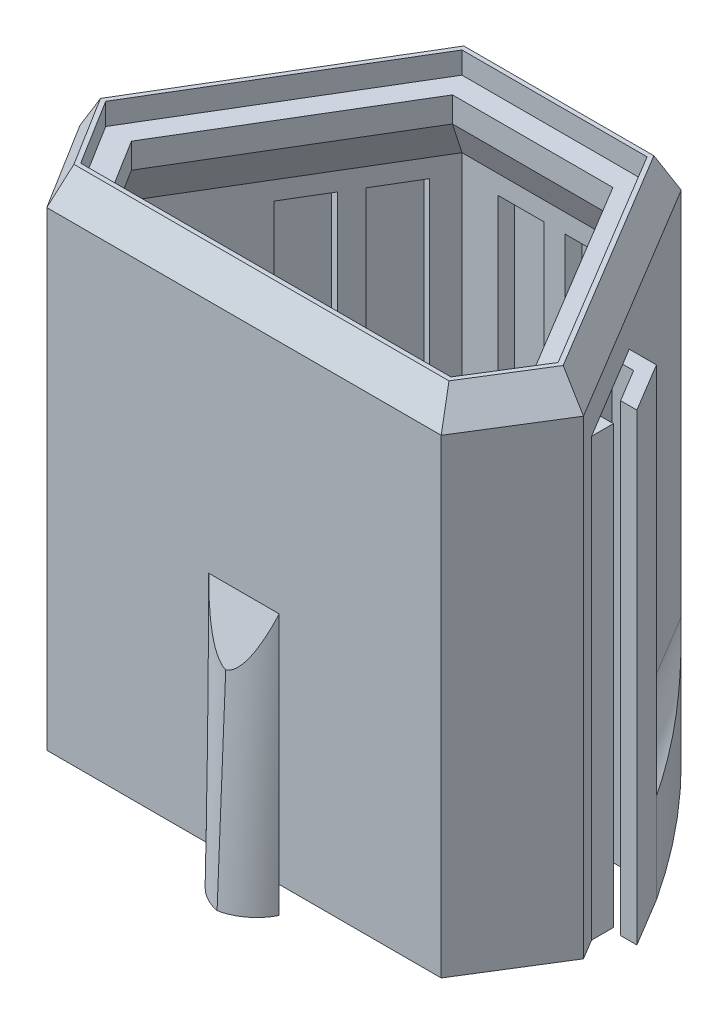
SolidWorks part; units mm, degrees
ref_plane "Front Plane" through (0, 0, 0) normal (0, 0, 1) x (1, 0, 0)
ref_plane "Top Plane" through (0, 0, 0) normal (0, 1, 0) x (1, 0, 0)
ref_plane "Right Plane" through (0, 0, 0) normal (1, 0, 0) x (0, 0, -1)
sketch "Sketch1" plane through (0, 0, 0) normal (0, 1, 0) x (1, 0, 0)
  line L0 (-12.5, 39.6) -> (12.5, 39.6)
  line L1 (-23.5, 0) -> (23.5, 0)
  line L2 (-11.0283, 37) -> (11.0283, 37)
  line L3 (11.0283, 37) -> (26.953, 10.474)
  line L4 (22.0553, 2.6) -> (26.953, 10.474)
  line L5 (-23.5, 0) -> (-30, 10.45)
  line L6 (-12.5, 39.6) -> (-30, 10.45)
  line L7 (12.5, 39.6) -> (30, 10.45)
  line L8 (23.5, 0) -> (30, 10.45)
  line L9 (-22.0553, 2.6) -> (22.0553, 2.6)
  line L10 (-22.0553, 2.6) -> (-26.953, 10.474)
  line L11 (-11.0283, 37) -> (-26.953, 10.474)
  dimension "D1" = 2.6
extrude "Boss-Extrude1" add sketch "Sketch1" along normal blind 60
sketch "Sketch4" plane through (0, 60, 0) normal (0, 1, 0) x (1, 0, 0)
  line L27 (-23.906, 10.4981) -> (-20.6106, 5.2)
  line L28 (-20.6106, 5.2) -> (20.6106, 5.2)
  line L29 (20.6106, 5.2) -> (23.906, 10.4981)
  line L30 (23.906, 10.4981) -> (9.5567, 34.4)
  line L31 (9.5567, 34.4) -> (-9.5567, 34.4)
  line L32 (-9.5567, 34.4) -> (-23.906, 10.4981)
  line L33 (-23.906, 10.4981) -> (-20.6106, 5.2)
  line L34 (-20.6106, 5.2) -> (20.6106, 5.2)
  line L35 (20.6106, 5.2) -> (23.906, 10.4981)
  line L36 (23.906, 10.4981) -> (9.5567, 34.4)
  line L37 (9.5567, 34.4) -> (-9.5567, 34.4)
  line L38 (-9.5567, 34.4) -> (-23.906, 10.4981)
  line L39 (-26.953, 10.474) -> (-22.0553, 2.6)
  line L43 (11.0283, 37) -> (-11.0283, 37)
  line L44 (-22.0553, 2.6) -> (22.0553, 2.6)
  line L45 (22.0553, 2.6) -> (26.953, 10.474)
  line L46 (26.953, 10.474) -> (11.0283, 37)
  line L47 (-11.0283, 37) -> (-26.953, 10.474)
  line L48 (11.0283, 37) -> (-11.0283, 37)
  line L49 (-22.0553, 2.6) -> (22.0553, 2.6)
  line L50 (22.0553, 2.6) -> (26.953, 10.474)
  line L51 (26.953, 10.474) -> (11.0283, 37)
  line L52 (-11.0283, 37) -> (-26.953, 10.474)
  line M18 (-22.0553, 2.6) -> (-26.953, 10.474)
  line M19 (-26.953, 10.474) -> (-11.0283, 37)
  line M20 (-11.0283, 37) -> (11.0283, 37)
  line M21 (11.0283, 37) -> (26.953, 10.474)
  line M22 (26.953, 10.474) -> (22.0553, 2.6)
  line M23 (22.0553, 2.6) -> (-22.0553, 2.6)
  dimension "D1" = 2.6
  dimension "D2" = 0
extrude "Boss-Extrude2" add sketch "Sketch4" against normal blind 10.6 contours L38 L37 L36 L35 L34 L33 M18 M23 M22 M21 M20 M19 region at (-18.4424, 60, -23.4079)
chamfer "Chamfer2" distance 4 distance2 2.08 6 edges at (26.75, 60, -5.225) (0, 60, 0) (-26.75, 60, -5.225) (-21.25, 60, -25.025) (0, 60, -39.6) (21.25, 60, -25.025) first distance on face at (26.75, 30, -5.225) first distance on face at (0, 30, 0) first distance on face at (-26.75, 30, -5.225) first distance on face at (-21.25, 30, -25.025) first distance on face at (0, 30, -39.6) first distance on face at (21.25, 30, -25.025)
sketch "Sketch5" plane through (0, 60, 0) normal (0, 1, 0) x (1, 0, 0)
  line L34 (-11.0283, 37) -> (-26.953, 10.474)
  line L35 (-26.953, 10.474) -> (-22.0553, 2.6)
  line L36 (-22.0553, 2.6) -> (22.0553, 2.6)
  line L37 (22.0553, 2.6) -> (26.953, 10.474)
  line L38 (26.953, 10.474) -> (11.0283, 37)
  line L39 (11.0283, 37) -> (-11.0283, 37)
  line L40 (-23.906, 10.4981) -> (-20.6106, 5.2)
  line L41 (-20.6106, 5.2) -> (20.6106, 5.2)
  line L42 (20.6106, 5.2) -> (23.906, 10.4981)
  line L43 (23.906, 10.4981) -> (9.5567, 34.4)
  line L44 (9.5567, 34.4) -> (-9.5567, 34.4)
  line L45 (-9.5567, 34.4) -> (-23.906, 10.4981)
  line L46 (-23.906, 10.4981) -> (-20.6106, 5.2)
  line L47 (-20.6106, 5.2) -> (20.6106, 5.2)
  line L48 (20.6106, 5.2) -> (23.906, 10.4981)
  line L49 (23.906, 10.4981) -> (9.5567, 34.4)
  line L50 (9.5567, 34.4) -> (-9.5567, 34.4)
  line L51 (-9.5567, 34.4) -> (-23.906, 10.4981)
  dimension "D1" = 0
  dimension "D2" = 2.6
extrude "Cut-Extrude1" cut sketch "Sketch5" against normal blind 2.6
sketch "Sketch6" plane through (0, 0, 0) normal (0, -1, 0) x (-1, 0, 0)
  line L0 (-28.5531, 12.8601) -> (-26.9922, 15.4601)
  line L1 (-28.5531, 12.8601) -> (-28.5531, 15.4601)
  line L2 (-28.5531, 15.4601) -> (-26.9922, 15.4601)
extrude "Boss-Extrude3" add sketch "Sketch6" against normal blind 52
sketch "Sketch7" plane through (0, 0, 0) normal (0, -1, 0) x (-1, 0, 0)
  line L0 (-26.9922, 15.4601) -> (-25.6922, 15.4601)
  line L1 (-26.9922, 15.4601) -> (-22.9775, 22.1475)
  line L2 (-26.9922, 15.4601) -> (-12.5, 39.6) construction
  line L3 (-22.9775, 22.1475) -> (-21.6775, 22.1475)
  line L4 (-21.6775, 22.1475) -> (-25.6922, 15.4601)
  dimension "D1" = 1.3
  dimension "D2" = 4.0148
extrude "Cut-Extrude2" cut sketch "Sketch7" against normal blind 52
sketch "Sketch8" plane through (0, 0, 0) normal (0, -1, 0) x (1, 0, 0)
  line L0 (22.9775, -22.1475) -> (24.2775, -22.1475)
  line L1 (24.2775, -22.1475) -> (26.6113, -18.2601)
  line L2 (21.8117, -24.0894) -> (22.9775, -22.1475)
  line L3 (26.6113, -18.2601) -> (28.5531, -18.2601)
  line L4 (28.5531, -18.2601) -> (25.0535, -24.0894)
  line L5 (25.0535, -24.0894) -> (21.8117, -24.0894)
  line L6 (22.9775, -22.1475) -> (12.5, -39.6) construction
extrude "Boss-Extrude4" add sketch "Sketch8" against normal blind 52
mirror "Mirror1" about plane through (0, 0, 0) normal (1, 0, 0) of "Boss-Extrude3", "Cut-Extrude2", "Boss-Extrude4"
chamfer "Chamfer3" distance 5 distance2 2.6 6 edges at (0, 49.4, -5.2) (22.2583, 49.4, -7.849) (16.7314, 49.4, -22.449) (0, 49.4, -34.4) (-22.2583, 49.4, -7.849) (-16.7314, 49.4, -22.449) first distance on face at (0, 53.4, -5.2) first distance on face at (22.2583, 53.4, -7.849) first distance on face at (16.7314, 53.4, -22.449) first distance on face at (0, 53.4, -34.4) first distance on face at (-22.2583, 53.4, -7.849) first distance on face at (-16.7314, 53.4, -22.449)
sketch "Sketch10" plane through (0, 0, 0) normal (0, -1, 0) x (1, 0, 0)
  line L0 (-12.5, -39.6) -> (-19.6941, -27.6167)
  line L1 (-25.0535, -24.0894) -> (-28.5531, -18.2601)
  line L2 (-28.5531, -18.2601) -> (-26.6113, -18.2601)
  line L3 (-26.6113, -18.2601) -> (-24.2775, -22.1475)
  line L4 (-12.5, -39.6) -> (-21.8117, -24.0894) construction
  line L5 (-19.6941, -27.6167) -> (-22.9775, -22.1475)
  line L6 (-22.9775, -22.1475) -> (-24.2775, -22.1475)
  arc A0 (-25.0535, -24.0894) -> (-12.5, -39.6) centre (55.9007, 28.5956) ccw
extrude "Boss-Extrude5" add sketch "Sketch10" along normal blind 3.2 and the other way blind 7
mirror "Mirror2" about plane through (0, 0, 0) normal (1, 0, 0) of "Boss-Extrude5"
fillet "Fillet1" radius 5 2 edges at (-17.1558, 7, -31.8447) (17.1558, 7, -31.8447)
sketch "Sketch11" plane through (0, 0, 0) normal (1, 0, 0) x (0, 0, -1)
  line L0 (0, 27.9211) -> (-2.1928, 21.0778)
  line L4 (0, -3.2) -> (-3.32, -3.2)
  line L5 (0, -3.2) -> (0, 27.9211)
  line L6 (0, 56) -> (0, 0) construction
  line L7 (-2.1928, 21.0778) -> (-3.32, -3.2)
extrude "Boss-Extrude7" add sketch "Sketch11" along normal blind 4.2 and the other way blind 4.2
fillet "Fillet7" radius 6 2 edges at (4.2, 8.9389, 2.7564) (-4.2, 8.9389, 2.7564)
sketch "Sketch12" plane through (0, 0, 0) normal (0, -1, 0) x (1, 0, 0)
  line L0 (-5.7805, -43.9113) -> (-7.5012, -39.6)
  line L1 (12.5, -39.6) -> (-12.5, -39.6) construction
  line L2 (-2.5248, -41.6113) -> (-2.5248, -43.9113)
  line L3 (-2.5248, -43.9113) -> (-5.7805, -43.9113)
  line L4 (-4.2221, -41.6113) -> (-5.0248, -39.6)
  line L5 (-4.2221, -41.6113) -> (-2.5248, -41.6113)
  line L10 (-7.5012, -39.6) -> (-5.0248, -39.6)
  point P2 (0, -39.6)
  dimension "D1" = 5.0248
extrude "Boss-Extrude8" add sketch "Sketch12" along normal blind 3 and the other way blind 44.2
fillet "Fillet8" radius 35 2 edges at (-6.6409, 44.2, -41.7556) (-4.1527, 44.2, -43.9113)
mirror "Mirror3" about plane through (0, 0, 0) normal (1, 0, 0) of "Boss-Extrude8", "Fillet8"
sketch "Sketch13" plane through (0, 0, -2.6) normal (0, 0, -1) x (-1, 0, 0)
  line L1 (-2.7757, 47.3986) -> (2.7243, 47.3986)
  line L2 (-2.7757, 47.3986) -> (-2.7757, 2.3986)
  line L3 (-2.7757, 2.3986) -> (2.7243, 2.3986)
  line L4 (2.7243, 47.3986) -> (2.7243, 2.3986)
  line L5 (-2.7757, 47.3986) -> (2.7243, 2.3986) construction
  line L6 (-2.7757, 2.3986) -> (2.7243, 47.3986) construction
  point P0 (-0.0257, 24.8986)
  dimension "D1" = 5.5
  dimension "D2" = 45
extrude "Cut-Extrude3" cut sketch "Sketch13" against normal blind 2
pattern_linear "LPattern1" count 3 spacing 8 along (1, 0, 0) count 3 spacing 8 along (-1, 0, 0) of "Cut-Extrude3"
sketch "Sketch14" plane through (-14.7366, 0, 9.1663) normal (0.8491, 0, -0.5282) x (-0.5282, 0, -0.8491)
  line L0 (13.8567, 24.7) -> (23.1297, 24.7) construction
  line L1 (15.7432, 2.2) -> (21.2432, 2.2)
  line L2 (15.7432, 2.2) -> (15.7432, 47.2)
  line L3 (15.7432, 47.2) -> (21.2432, 47.2)
  line L4 (21.2432, 2.2) -> (21.2432, 47.2)
  line L5 (15.7432, 2.2) -> (21.2432, 47.2) construction
  line L6 (15.7432, 47.2) -> (21.2432, 2.2) construction
  line L7 (13.8567, 49.4) -> (13.8567, 0) construction
  line L8 (23.1297, 49.4) -> (23.1297, 0) construction
  point P0 (18.4932, 24.7)
  dimension "D1" = 5.5
  dimension "D2" = 45
extrude "Cut-Extrude4" cut sketch "Sketch14" against normal blind 2
sketch "Sketch15" plane through (14.7366, 0, 9.1663) normal (-0.8491, 0, -0.5282) x (-0.5282, 0, 0.8491)
  line L0 (-13.8567, 24.7) -> (-23.1297, 24.7) construction
  line L1 (-13.8567, 49.4) -> (-13.8567, 0) construction
  line L2 (-23.1297, 49.4) -> (-23.1297, 0) construction
  line L4 (-21.2432, 2.2) -> (-15.7432, 2.2)
  line L5 (-21.2432, 2.2) -> (-21.2432, 47.2)
  line L6 (-21.2432, 47.2) -> (-15.7432, 47.2)
  line L7 (-15.7432, 2.2) -> (-15.7432, 47.2)
  line L8 (-21.2432, 2.2) -> (-15.7432, 47.2) construction
  line L9 (-21.2432, 47.2) -> (-15.7432, 2.2) construction
  point P6 (-18.4932, 24.7)
  dimension "D1" = 5.5
  dimension "D2" = 45
extrude "Cut-Extrude5" cut sketch "Sketch15" against normal blind 2
sketch "Sketch16" plane through (0, 0, -37) normal (0, 0, 1) x (1, 0, 0)
  line L0 (0, 0) -> (0, 2.1454) construction
  line L1 (-11.0283, 49.4) -> (11.0283, 49.4) construction
  line L2 (0, 47.1454) -> (0, 49.4) construction
  line L3 (1.25, 2.1454) -> (6.75, 2.1454)
  line L4 (1.25, 2.1454) -> (1.25, 47.1454)
  line L5 (1.25, 47.1454) -> (6.75, 47.1454)
  line L6 (6.75, 2.1454) -> (6.75, 47.1454)
  line L7 (1.25, 2.1454) -> (6.75, 47.1454) construction
  line L8 (1.25, 47.1454) -> (6.75, 2.1454) construction
  point P5 (4, 24.6454)
  dimension "D1" = 5.5
  dimension "D2" = 45
extrude "Cut-Extrude6" cut sketch "Sketch16" against normal blind 2
pattern_linear "LPattern2" count 2 spacing 8 along (-1, 0, 0) of "Cut-Extrude6"
sketch "Sketch18" plane through (24.4345, 0, -14.6691) normal (-0.8574, 0, 0.5147) x (0.5147, 0, 0.8574)
  line L4 (-15.2298, 2.2) -> (-9.7298, 2.2)
  line L5 (-15.2298, 2.2) -> (-15.2298, 47.2)
  line L6 (-15.2298, 47.2) -> (-9.7298, 47.2)
  line L7 (-9.7298, 2.2) -> (-9.7298, 47.2)
  line L8 (-15.2298, 2.2) -> (-9.7298, 47.2) construction
  line L9 (-15.2298, 47.2) -> (-9.7298, 2.2) construction
  dimension "D1" = 5.5
  dimension "D2" = 45
extrude "Cut-Extrude7" cut sketch "Sketch18" against normal blind 2
pattern_linear "LPattern3" count 2 spacing 8 along (-0.5147, 0, -0.8574) of "Cut-Extrude7"
mirror "Mirror4" about plane through (0, 0, 0) normal (1, 0, 0) of "LPattern3", "Cut-Extrude7"
